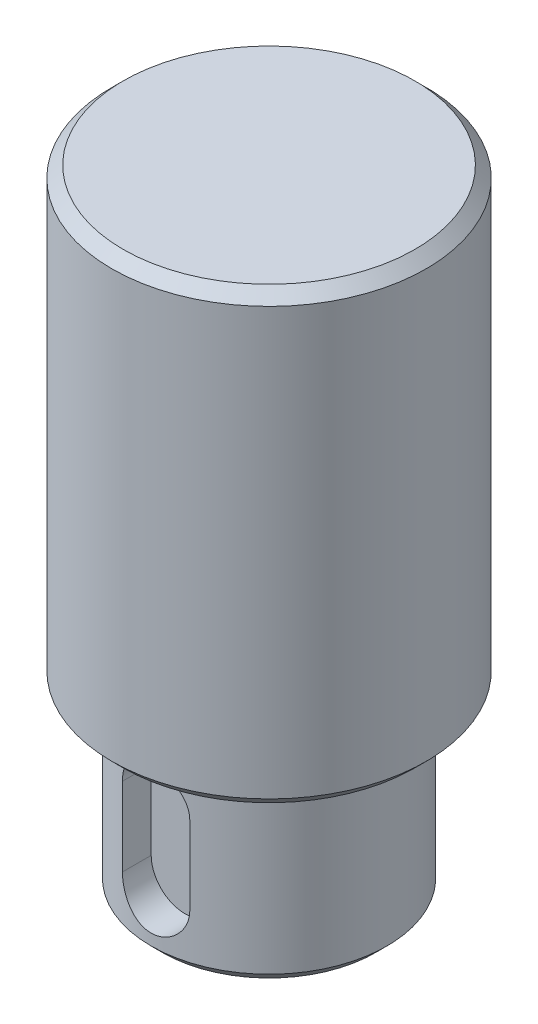
SolidWorks part; units mm, degrees
ref_plane "Front Plane" through (0, 0, 0) normal (0, 0, 1) x (1, 0, 0)
ref_plane "Top Plane" through (0, 0, 0) normal (0, 1, 0) x (1, 0, 0)
ref_plane "Right Plane" through (0, 0, 0) normal (1, 0, 0) x (0, 0, -1)
sketch "Sketch3" plane through (0, 0, 0) normal (0, 1, 0) x (1, 0, 0)
  circle A0 centre (0, 0) radius 10.5
  circle A1 centre (0, 0) radius 14
extrude "Boss-Extrude2" add sketch "Sketch3" along normal blind 56 contours A0 | A1 A0 region at (0, 0, 0) region at (-13.604, 0, 0)
extrude "Cut-Extrude1" cut sketch "Sketch3<4>" along normal blind 16
sketch "Sketch3<4>" plane through (0, 0, 0) normal (0, 1, 0) x (1, 0, 0) same geometry as "Sketch3"
ref_plane "Plane1" through (0, 0, 7.5) normal (0, 0, 1) x (1, 0, 0)
chamfer "Chamfer1" distance 1 angle 45 3 edges at (0, 56, 14) (0, 16, 14) (0, 0, 10.5)
sketch "Sketch5" plane through (0, 0, 7.5) normal (0, 0, 1) x (1, 0, 0)
  line L1 (0, 5) -> (0, 12) construction
  line L3 (-3, 5) -> (-3, 12)
  line L4 (3, 5) -> (3, 12)
  arc A0 (-3, 5) -> (3, 5) centre (0, 5) ccw
  arc A1 (3, 12) -> (-3, 12) centre (0, 12) ccw
  point P6 (0, 8.5)
extrude "Cut-Extrude2" cut sketch "Sketch5" along normal blind 16
